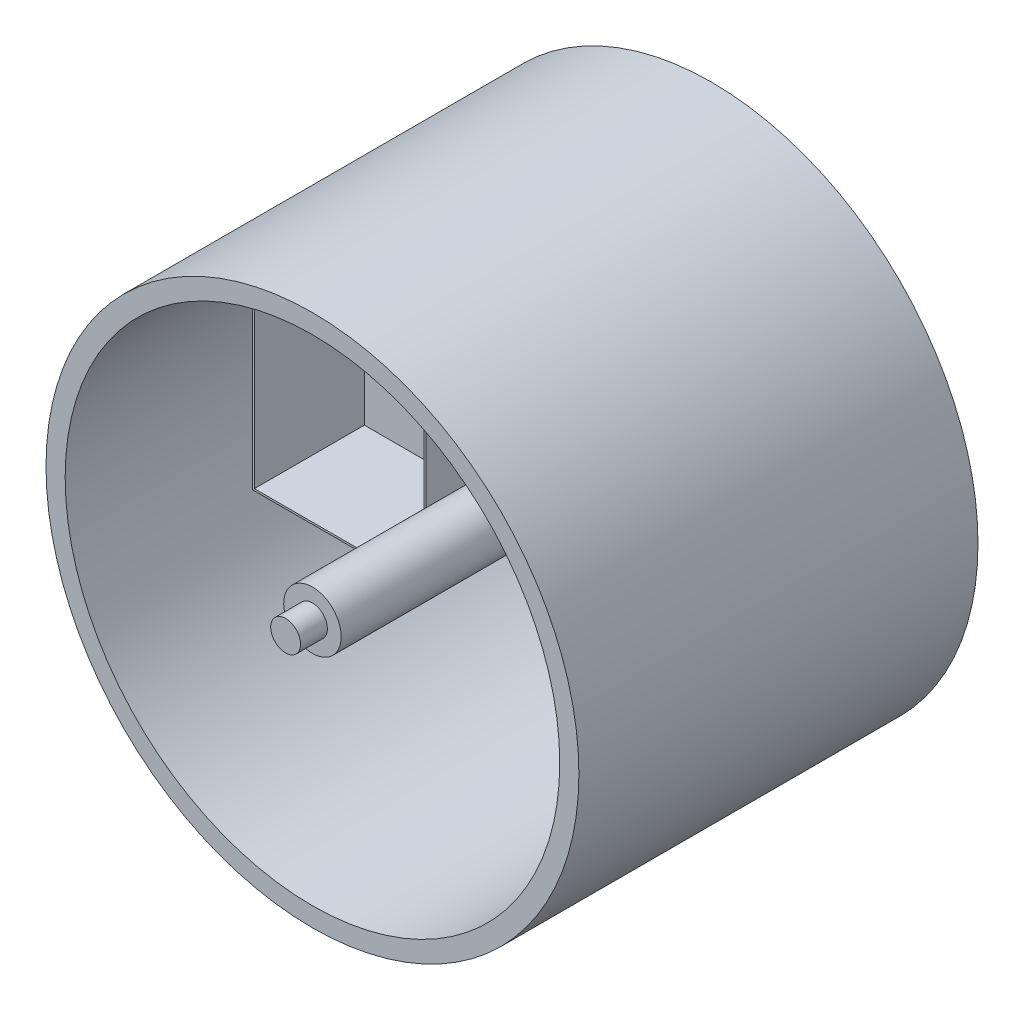
SolidWorks part; units mm, degrees
ref_plane "Front Plane" through (0, 0, 0) normal (0, 0, 1) x (1, 0, 0)
ref_plane "Top Plane" through (0, 0, 0) normal (0, 1, 0) x (1, 0, 0)
ref_plane "Right Plane" through (0, 0, 0) normal (1, 0, 0) x (0, 0, -1)
sketch "Sketch1" plane through (0, 0, 0) normal (0, 0, 1) x (1, 0, 0)
  line L1 (-58.455, -21.15) -> (-16.155, -21.15)
  line L2 (-58.455, -21.15) -> (-58.455, 21.15)
  line L3 (-58.455, 21.15) -> (-16.155, 21.15)
  line L4 (-16.155, -21.15) -> (-16.155, 21.15)
  line L5 (-58.455, -21.15) -> (-16.155, 21.15) construction
  line L6 (-58.455, 21.15) -> (-16.155, -21.15) construction
  circle A0 centre (0, 0) radius 69.53
  circle A1 centre (0, 0) radius 42.465 construction
  circle A3 centre (-37.305, 0) radius 5.16 construction
  dimension "D1" = 139.06
  dimension "D2" = 84.93
  dimension "D4" = 10.32
  dimension "D5" = 42.3
  dimension "D6" = 42.3
extrude "Boss-Extrude1" add sketch "Sketch1" along normal blind 104.14 contours A0 L4 L1 L2 L3 | L1 L4 L3 L2 region at (-37.305, 0, 0) region at (4.9819, 0, 0)
shell "Shell1" thickness 5 removed face at (69.53, 0, 104.14)
extrude "Boss-Extrude3" add sketch "Sketch1<4>" along normal blind 31.14 contours L3 L4 L1 L2
sketch "Sketch1<4>" plane through (0, 0, 0) normal (0, 0, 1) x (1, 0, 0) same geometry as "Sketch1"
sketch "Sketch2" plane through (0, 0, 31.14) normal (0, 0, 1) x (1, 0, 0)
  line L2 (-16.155, -21.15) -> (-16.155, 21.15) construction
  line L4 (-58.455, -20.7541) -> (-58.455, 20.7541)
  line L5 (-58.3129, -21.15) -> (-16.155, -21.15)
  line L6 (-16.155, -21.15) -> (-16.155, 21.15)
  line L7 (-58.3129, 21.15) -> (-16.155, 21.15)
  line L8 (-58.455, 0) -> (-16.155, 0) construction
  line L10 (-59.955, -22.65) -> (-14.655, -22.65)
  line L11 (-59.955, -22.65) -> (-59.955, 22.65)
  line L12 (-59.955, 22.65) -> (-14.655, 22.65)
  line L13 (-14.655, -22.65) -> (-14.655, 22.65)
  line L14 (-59.955, -22.65) -> (-14.655, 22.65) construction
  line L15 (-59.955, 22.65) -> (-14.655, -22.65) construction
  arc A2 (-58.455, -20.7541) -> (-58.3129, -21.15) centre (0, 0) ccw
  arc A3 (-58.3129, 21.15) -> (-58.455, 20.7541) centre (0, 0) ccw
  point P8 (-37.305, 0)
  point P9 (-58.455, 0)
  dimension "D1" = 1.5
extrude "Boss-Extrude5" add sketch "Sketch2" along normal blind 28.7 and the other way up to next
sketch "Sketch3" plane through (0, 0, 59.84) normal (0, 0, 1) x (1, 0, 0)
  line L0 (-15.155, 22.15) -> (-15.155, -22.15)
  line L1 (-15.155, -22.15) -> (-59.455, -22.15)
  line L2 (-59.455, -22.15) -> (-59.455, 22.15)
  line L3 (-59.455, 22.15) -> (-15.155, 22.15)
  line L4 (-16.155, 21.15) -> (-58.3129, 21.15) construction
  line L5 (-16.155, -21.15) -> (-16.155, 21.15) construction
  line L6 (-58.455, 20.7541) -> (-58.455, -20.7541) construction
  line L7 (-58.3129, -21.15) -> (-16.155, -21.15) construction
  line M7 (-58.3129, 21.15) -> (-16.155, 21.15)
  line M8 (-16.155, 21.15) -> (-16.155, -21.15)
  line M9 (-16.155, -21.15) -> (-58.3129, -21.15)
  arc M20 (-58.3129, -21.15) -> (-58.455, -20.7541) centre (0, 0) cw
  line M21 (-58.455, -20.7541) -> (-58.455, 20.7541)
  arc M22 (-58.455, 20.7541) -> (-58.3129, 21.15) centre (0, 0) cw
  dimension "D1" = 1
  dimension "D2" = 1
  dimension "D3" = 1
  dimension "D4" = 1
extrude "Cut-Extrude1" cut sketch "Sketch3" against normal up to surface (28.7 mm away) contours L3 L2 L1 L0 M9 M20 M21 M22 M7 M8 region at (-15.7815, 0, 59.84) up to face at (-44.3078, 0, 31.14)
sketch "Sketch4" plane through (0, 0, 5) normal (0, 0, 1) x (1, 0, 0)
  circle A0 centre (0, 0) radius 7.5
  dimension "D1" = 15
extrude "Boss-Extrude6" add sketch "Sketch4" along normal blind 99.14
sketch "Sketch5" plane through (0, 0, 104.14) normal (0, 0, 1) x (1, 0, 0)
  circle A0 centre (0, 0) radius 3.9
  dimension "D1" = 7.8
extrude "Boss-Extrude7" add sketch "Sketch5" along normal blind 7
equation "\"planetary_gear_diameter\"= 3.9in"
equation "\"planetary_gear_pitch_diameter\"= 84.93"
equation "\"20T_gear_pitch_diameter\"= 50.16"
equation "\"10T_gear_pitch_diameter\"= 10.32"
equation "\"D1@Sketch1\" = \"planetary_gear_diameter\" + 40mm"
equation "\"D2@Sketch1\"= \"planetary_gear_pitch_diameter\""
equation "\"D4@Sketch1\"= \"10T_gear_pitch_diameter\""
